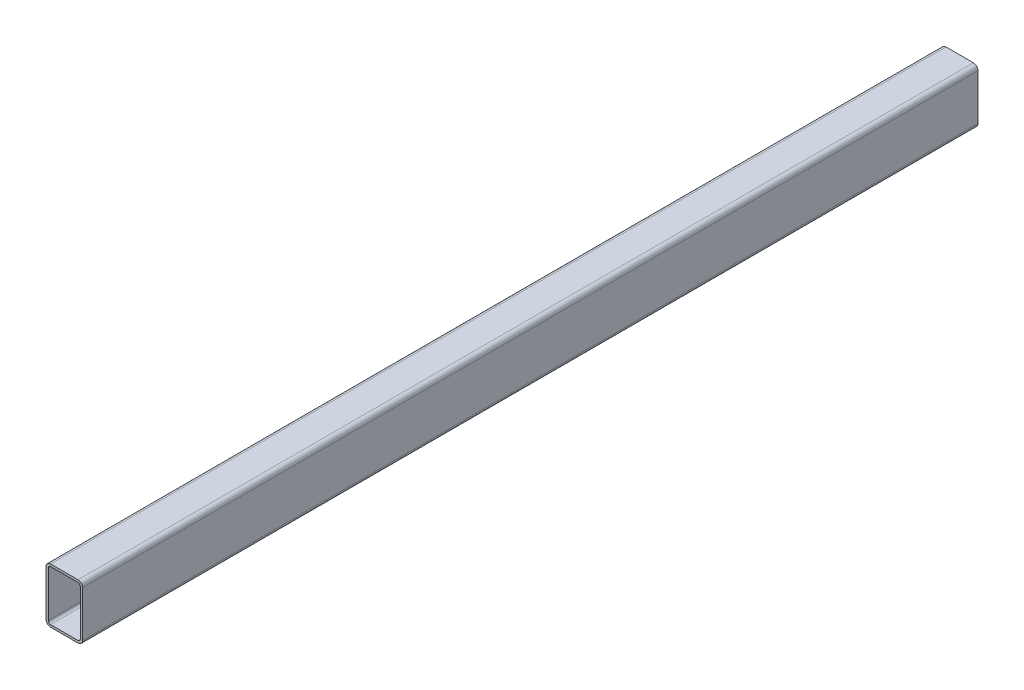
SolidWorks part; units mm, degrees
material "Plain Carbon Steel"
ref_plane "Front Plane" through (0, 0, 0) normal (0, 0, 1) x (1, 0, 0)
ref_plane "Top Plane" through (0, 0, 0) normal (0, 1, 0) x (1, 0, 0)
ref_plane "Right Plane" through (0, 0, 0) normal (1, 0, 0) x (0, 0, -1)
sketch "Sketch13" plane through (0, 0, 0) normal (0, 0, 1) x (1, 0, 0)
  line L4 (19.05, -38.1) -> (-19.05, -38.1)
  line L5 (25.4, 31.75) -> (25.4, -31.75)
  line L6 (-25.4, -31.75) -> (-25.4, 31.75)
  line L7 (-19.05, 38.1) -> (19.05, 38.1)
  line L8 (19.05, -34.925) -> (-19.05, -34.925)
  line L9 (22.225, 31.75) -> (22.225, -31.75)
  line L10 (-19.05, 34.925) -> (19.05, 34.925)
  line L11 (-22.225, -31.75) -> (-22.225, 31.75)
  line L12 (-19.05, 31.75) -> (19.05, -31.75) construction
  line L13 (19.05, 31.75) -> (-19.05, -31.75) construction
  arc A4 (-25.4, -31.75) -> (-19.05, -38.1) centre (-19.05, -31.75) ccw
  arc A5 (19.05, -38.1) -> (25.4, -31.75) centre (19.05, -31.75) ccw
  arc A6 (25.4, 31.75) -> (19.05, 38.1) centre (19.05, 31.75) ccw
  arc A7 (-19.05, 38.1) -> (-25.4, 31.75) centre (-19.05, 31.75) ccw
  arc A8 (-22.225, -31.75) -> (-19.05, -34.925) centre (-19.05, -31.75) ccw
  arc A9 (19.05, -34.925) -> (22.225, -31.75) centre (19.05, -31.75) ccw
  arc A10 (22.225, 31.75) -> (19.05, 34.925) centre (19.05, 31.75) ccw
  arc A11 (-19.05, 34.925) -> (-22.225, 31.75) centre (-19.05, 31.75) ccw
  point P24 (0, 0)
  dimension "D4" = 6.35
  dimension "D2" = 50.8
  dimension "D3" = 76.2
  dimension "D1" = 3.175
extrude "Boss-Extrude2" add sketch "Sketch13" along normal mid plane 1244.6 separate body
equation "\"M5_tap\"=4.2mm       ' Below you can do mesurements as follows: cm, mm, ft, in, m, "
equation "\"M5_clearence\"=5.5mm"
equation "\"M6_tap\"=5mm"
equation "\"M6_clearence\"=6.6mm"
